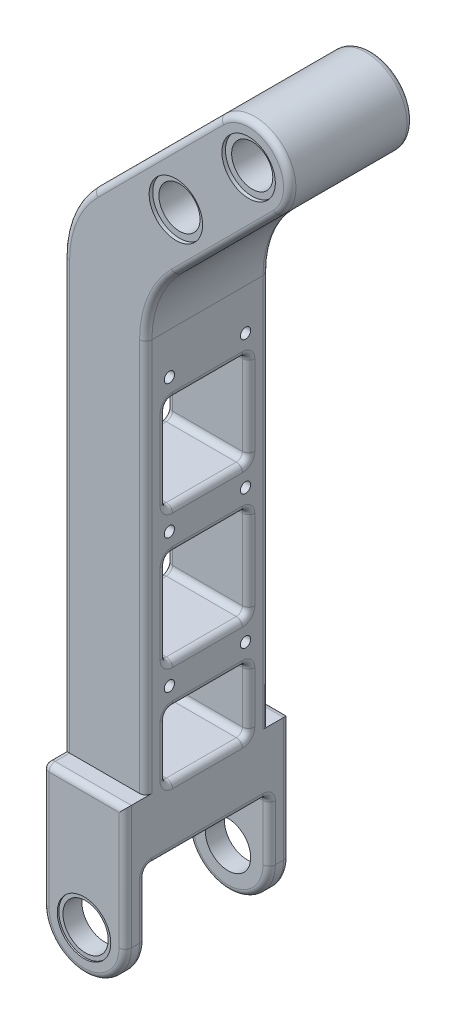
SolidWorks part; units mm, degrees
material "6061 合金"
ref_plane "前视基准面" through (0, 0, 0) normal (0, 0, 1) x (1, 0, 0)
ref_plane "上视基准面" through (0, 0, 0) normal (0, 1, 0) x (1, 0, 0)
ref_plane "右视基准面" through (0, 0, 0) normal (1, 0, 0) x (0, 0, -1)
other "Configuration Table"
sketch "草图1" plane through (0, 0, 0) normal (0, 0, 1) x (1, 0, 0)
  circle A0 centre (0, 0) radius 20
  circle A1 centre (0, 0) radius 10
  dimension "D1" = 40
  dimension "D2" = 20
extrude "凸台-拉伸1" add sketch "草图1" along normal blind 60 contours A1 | A0 region at (0, 0, 0)
ref_plane "基准面1" through (0, 0, 30) normal (0, 0, 1) x (1, 0, 0)
sketch "草图2" plane through (0, 0, 30) normal (0, 0, 1) x (1, 0, 0)
  line L0 (0, 0) -> (-70, -70) construction
  line L1 (-70, -70) -> (-70, -320) construction
  line L2 (0, -57.3148) -> (0, 49.9409) construction
  line L3 (-56.8582, 0) -> (46.4003, 0) construction
  line L4 (-14.1421, 14.1421) -> (-90, -61.7157)
  line L5 (14.1421, -14.1421) -> (-50, -78.2843)
  line L6 (-90, -61.7157) -> (-90, -320)
  line L7 (-50, -78.2843) -> (-50, -320)
  line L8 (-90, -320) -> (-50, -320)
  circle A2 centre (0, 0) radius 20 construction
  arc A3 (-14.1421, 14.1421) -> (14.1421, -14.1421) centre (0, 0) ccw
  dimension "D1" = 45
  dimension "D2" = 250
  dimension "D3" = 70
  dimension "D4" = 40
  dimension "D5" = 40
extrude "凸台-拉伸2" add sketch "草图2" along normal mid plane 60 contours L7 L8 L6 L4 A3 L5
sketch "草图4" plane through (0, 0, 60) normal (0, 0, 1) x (1, 0, 0)
  line L0 (-90, -61.7157) -> (-90, -320) construction
  line L1 (-90, -290) -> (-50, -290)
  line L2 (-90, -290) -> (-90, -350)
  line L4 (-50, -290) -> (-50, -350)
  line L5 (-50, -78.2843) -> (-50, -320) construction
  line L6 (-90, -320) -> (-50, -320) construction
  arc A0 (-90, -350) -> (-50, -350) centre (-70, -350) ccw
  circle A1 centre (-70, -350) radius 11
  dimension "D3" = 22
  dimension "D1" = 30
  dimension "D2" = 30
extrude "凸台-拉伸3" add sketch "草图4" along normal blind 10
mirror "镜向1" about plane through (0, 0, 30) normal (0, 0, 1) of "凸台-拉伸3"
sketch "草图5" plane through (0, 0, 0) normal (0, 1, 0) x (1, 0, 0)
  line L0 (0, 0) -> (0, -78.0582) construction
ref_plane "基准面2" through (-70, 0, 0) normal (-1, 0, 0) x (0, 0, 1)
sketch "草图7" plane through (-70, 0, 0) normal (-1, 0, 0) x (0, 0, 1)
  line L0 (-34.1239, -350) -> (109.535, -350) construction
sketch "草图8" plane through (0, 0, 60) normal (0, 0, 1) x (1, 0, 0)
  line L0 (0, 0) -> (-70, -70) construction
  circle A0 centre (-35.3553, -35.3553) radius 10
  dimension "D1" = 20
  dimension "D2" = 50
extrude "切除-拉伸1" cut sketch "草图8" against normal blind 100
fillet "圆角1" radius 50 2 edges at (-90, -61.7157, 30) (-50, -78.2843, 30)
fillet "圆角2" radius 3 34 edges at (-50, -320, 70) (-70, -370, 70) (-50, -335, 60) (-70, -370, 60) (-50, -335, 0) (-70, -370, 0) (-50, -320, -10) (-70, -370, -10) (-70, -320, 60) (-50, -320, 30) (-70, -320, 0) (-90, -290, 65) (-90, -320, 70) (-90, -335, 60) (-90, -320, 30) (-90, -335, 0) (-90, -320, -10) (-90, -290, -5) (-50, -194.4975, 0) (-46.194, -79.8608, 0) (-10.6066, -38.8909, 0) (14.1421, 14.1421, 0) (-44.7487, -16.4645, 0) (-86.194, -63.2922, 0) (-90, -186.2132, 0) (14.1421, 14.1421, 60) (-10.6066, -38.8909, 60) (-46.194, -79.8608, 60) (-50, -194.4975, 60) (-90, -186.2132, 60) (-86.194, -63.2922, 60) (-44.7487, -16.4645, 60) (-70, -290, 70) (-70, -290, -10)
sketch "草图9" plane through (0, 0, 70) normal (0, 0, 1) x (1, 0, 0)
  circle A0 centre (-70, -350) radius 13
  dimension "D1" = 26
extrude "切除-拉伸2" cut sketch "草图9" against normal blind 0.75
sketch "草图10" plane through (0, 0, -10) normal (0, 0, -1) x (-1, 0, 0)
  circle A0 centre (70, -350) radius 13
  dimension "D1" = 26
extrude "切除-拉伸3" cut sketch "草图10" against normal blind 0.75 contours A0
sketch "草图11" plane through (-90, 0, 0) normal (-1, 0, 0) x (0, 0, 1)
  circle A0 centre (48.5, -118.9949) radius 2.5
  circle A1 centre (48.5, -183.9949) radius 2.5
  circle A2 centre (48.5, -248.9949) radius 2.5
  circle A3 centre (11.5, -248.9949) radius 2.5
  circle A4 centre (11.5, -183.9949) radius 2.5
  circle A5 centre (11.5, -118.9949) radius 2.5
  point P18 (0, 0)
  dimension "D1" = 5
extrude "切除-拉伸4" cut sketch "草图11" against normal through all contours A1 | A2 | A0 | A3 | A4 | A5 region at (-90, -183.9949, 48.5) region at (-90, -248.9949, 48.5)
sketch "草图12" plane through (-90, 0, 0) normal (-1, 0, 0) x (0, 0, 1)
  line L0 (30, -62.0134) -> (30, -339.6946) construction
  line L1 (10, -128.9949) -> (50, -128.9949)
  line L2 (10, -128.9949) -> (10, -173.9949)
  line L3 (10, -173.9949) -> (50, -173.9949)
  line L4 (50, -128.9949) -> (50, -173.9949)
  line L5 (10, -193.9949) -> (50, -193.9949)
  line L6 (10, -193.9949) -> (10, -238.9949)
  line L7 (10, -238.9949) -> (50, -238.9949)
  line L8 (50, -193.9949) -> (50, -238.9949)
  line L9 (10, -258.9949) -> (50, -258.9949)
  line L10 (10, -258.9949) -> (10, -290)
  line L11 (10, -290) -> (50, -290)
  line L12 (50, -258.9949) -> (50, -290)
  line L13 (19.5, -173.9949) -> (40.5, -173.9949)
  line L14 (19.5, -173.9949) -> (19.5, -193.9949)
  line L15 (19.5, -193.9949) -> (40.5, -193.9949)
  line L16 (40.5, -173.9949) -> (40.5, -193.9949)
  line L17 (19.5, -238.9949) -> (40.5, -238.9949)
  line L18 (19.5, -238.9949) -> (19.5, -258.9949)
  line L19 (19.5, -258.9949) -> (40.5, -258.9949)
  line L20 (40.5, -238.9949) -> (40.5, -258.9949)
  line L21 (60, -82.4264) -> (60, -290) construction
  line L22 (0, -290) -> (0, -82.4264) construction
  line L23 (57, -320) -> (3, -320) construction
  circle A0 centre (48.5, -118.9949) radius 2.5 construction
  circle A1 centre (48.5, -183.9949) radius 2.5 construction
  circle A2 centre (48.5, -248.9949) radius 2.5 construction
  dimension "D1" = 10
  dimension "D2" = 10
  dimension "D3" = 10
  dimension "D4" = 8
  dimension "D5" = 10
  dimension "D6" = 10
  dimension "D7" = 10
  dimension "D8" = 30
extrude "减重" cut sketch "草图12" against normal through all contours L0 L1 L2 L3 | L15 L0 L17 L7 L8 L5 | L0 L5 L6 L7 | L19 L0 L11 L12 L9 | L0 L9 L10 L11 | L1 L0 L13 L3 L4 region at (-90, -151.4949, 40) region at (-90, -151.4949, 20) region at (-90, -216.4949, 40) region at (-90, -216.4949, 20) region at (-90, -274.4975, 40) region at (-90, -274.4975, 20)
fillet "圆角3" radius 3 36 edges at (-90, -258.9949, 30) (-50, -258.9949, 30) (-50, -290, 30) (-90, -290, 30) (-50, -238.9949, 30) (-50, -193.9949, 30) (-90, -193.9949, 30) (-90, -238.9949, 30) (-50, -173.9949, 30) (-90, -173.9949, 30) (-50, -128.9949, 30) (-90, -128.9949, 30) (-70, -290, 10) (-90, -274.4975, 10) (-70, -258.9949, 10) (-50, -274.4975, 10) (-50, -274.4975, 50) (-70, -258.9949, 50) (-90, -274.4975, 50) (-70, -290, 50) (-50, -216.4949, 50) (-70, -193.9949, 50) (-90, -216.4949, 50) (-70, -238.9949, 50) (-70, -238.9949, 10) (-90, -216.4949, 10) (-70, -193.9949, 10) (-50, -216.4949, 10) (-70, -173.9949, 10) (-90, -151.4949, 10) (-70, -128.9949, 10) (-50, -151.4949, 10) (-50, -151.4949, 50) (-70, -128.9949, 50) (-90, -151.4949, 50) (-70, -173.9949, 50)
sketch "草图13" plane through (0, 0, 60) normal (0, 0, 1) x (1, 0, 0)
  circle A0 centre (0, 0) radius 13
  circle A1 centre (-35.3553, -35.3553) radius 13
  dimension "D1" = 26
  dimension "D2" = 26
extrude "切除-拉伸6" cut sketch "草图13" against normal blind 1.75
sketch "草图14" plane through (0, 0, 0) normal (0, 0, -1) x (-1, 0, 0)
  circle A0 centre (0, 0) radius 13
  circle A1 centre (35.3553, -35.3553) radius 13
  dimension "D1" = 26
  dimension "D2" = 26
extrude "切除-拉伸7" cut sketch "草图14" against normal blind 1.75
